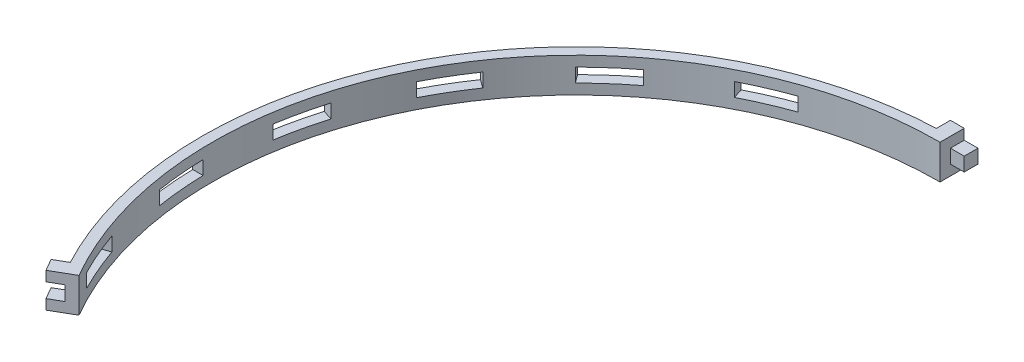
SolidWorks part; units mm, degrees
note: '?' marks a value the reader was unsure of.
ref_plane "Front Plane" through (0, 0, 0) normal (0, 0, 1) x (1, 0, 0)
ref_plane "Top Plane" through (0, 0, 0) normal (0, 1, 0) x (1, 0, 0)
ref_plane "Right Plane" through (0, 0, 0) normal (1, 0, 0) x (0, 0, -1)
sketch "Sketch1" plane through (0, 0, 0) normal (0, 1, 0) x (1, 0, 0)
  line L0 (108.5, 0) -> (105.5, 0) construction
  line L1 (0, 108.5) -> (0, -108.5)
  line L6 (0, 0) -> (-215.0076, 0) construction
  line L7 (0, 0) -> (-93.9638, -54.25)
  line L17 (0, 108.5) -> (0, 105.5)
  line L18 (0, 106) -> (-4, 106)
  line L19 (0, 106) -> (0, 112.5)
  line L20 (0, 112.5) -> (-4, 112.5)
  line L21 (-4, 106) -> (-4, 112.5)
  line L22 (-91.7987, -53) -> (-97.4279, -56.25)
  line L23 (-97.4279, -56.25) -> (-99.4279, -52.7859)
  line L24 (-99.4279, -52.7859) -> (-93.7987, -49.5359)
  line L25 (-93.7987, -49.5359) -> (-91.7987, -53)
  circle A0 centre (0, 0) radius 105.5
  circle A1 centre (0, 0) radius 108.5
  dimension "D1" = 211
  dimension "D2" = 3
  dimension "D3" = 120
  dimension "D4" = 4
  dimension "D5" = 4
  dimension "D6" = 4
  dimension "D7" = 4
  dimension "D8" = 106
  dimension "D9" = 106
extrude "Boss-Extrude1" add sketch "Sketch1" along normal blind 10
ref_axis "Axis1" through (0, 10, 0) along (0, -1, 0)?
sketch "Sketch2" plane through (-97.4279, 0, 56.25) normal (-0.866, 0, 0.5) x (0.5, 0, 0.866)
  line L1 (-4, 7.1) -> (4, 7.1)
  line L2 (-4, 7.1) -> (-4, 2.9)
  line L3 (-4, 2.9) -> (4, 2.9)
  line L4 (4, 7.1) -> (4, 2.9)
  line L5 (-4, 10) -> (-4, 0) construction
  point P6 (-4, 5)
  point P7 (-4, 5)
  dimension "D1" = 4.2
  dimension "D2" = 8
extrude "Cut-Extrude1" cut sketch "Sketch2" against normal blind 4
sketch "Sketch3" plane through (0, 0, -112.5) normal (0, 0, -1) x (-1, 0, 0)
  line L1 (4, 3) -> (-4, 3)
  line L2 (4, 3) -> (4, 7)
  line L3 (4, 7) -> (-4, 7)
  line L4 (-4, 3) -> (-4, 7)
  line L5 (4, 10) -> (4, 0) construction
  point P6 (4, 5)
  point P7 (4, 5)
  dimension "D2" = 8
  dimension "D1" = 4
extrude "Boss-Extrude2" add sketch "Sketch3" against normal blind 4 contours L2 L1 L4 L3
sketch "Sketch4" plane through (0, 0, 0) normal (1, 0, 0) x (0, 0, -1)
  line L0 (-50.749, 0) -> (108.4262, 0) construction
  line L1 (-2.6723, 7) -> (-16.6723, 7)
  line L2 (-2.6723, 7) -> (-2.6723, 3)
  line L3 (-2.6723, 3) -> (-16.6723, 3)
  line L4 (-16.6723, 7) -> (-16.6723, 3)
  line L5 (108.4262, 10) -> (-50.749, 10) construction
  dimension "D1" = 3
  dimension "D2" = 3
  dimension "D3" = 14
extrude "Cut-Extrude2" cut sketch "Sketch4" against normal through all
pattern_circular "CirPattern4" count 5 every 18 about axis through (0, 0, 0) along (0, 1, 0) of "Cut-Extrude2"
equation "\"key_height\"= 4mm"
equation "\"slot_height\"= \"key_height\" + 0.2mm"
equation "\"D1@Sketch2\"=\"slot_height\""
equation "\"D1@Sketch3\"=\"key_height\""
